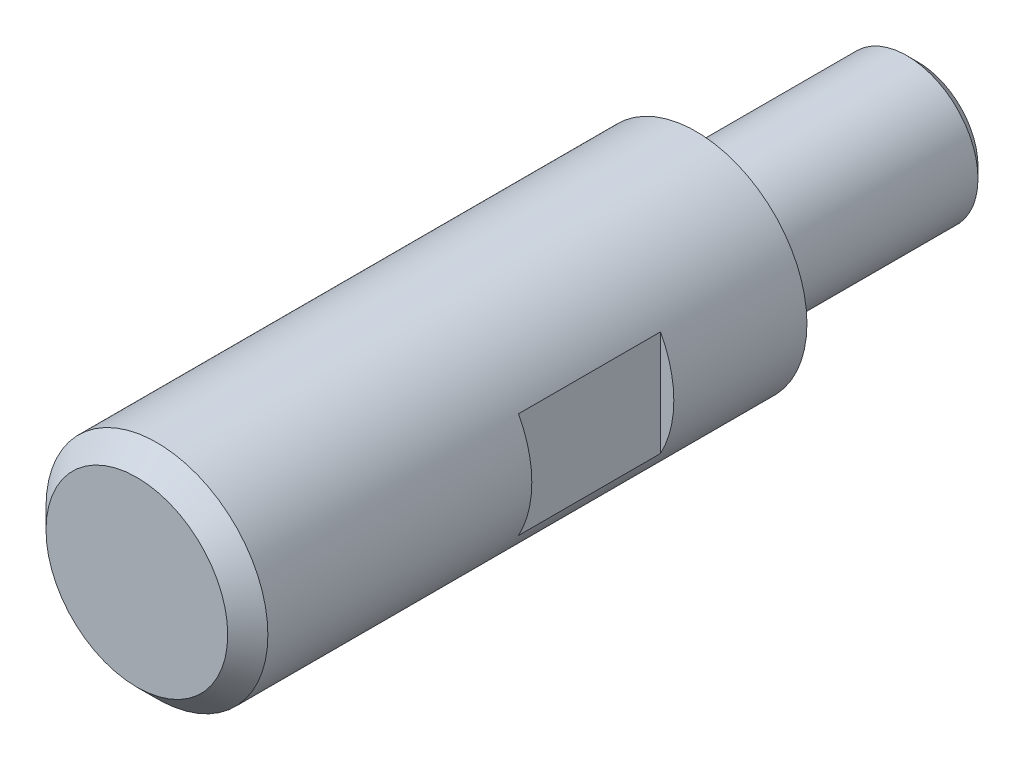
SolidWorks part; units mm, degrees
ref_plane "Płaszczyzna przednia" through (0, 0, 0) normal (0, 0, 1) x (1, 0, 0)
ref_plane "Płaszczyzna górna" through (0, 0, 0) normal (0, 1, 0) x (1, 0, 0)
ref_plane "Płaszczyzna prawa" through (0, 0, 0) normal (1, 0, 0) x (0, 0, -1)
sketch "Szkic1" plane through (0, 0, 0) normal (0, 1, 0) x (1, 0, 0)
  line L0 (11, -40) -> (11, -56)
  line L1 (11, -56) -> (15, -56)
  line L2 (15, -56) -> (15, -40)
  line L3 (15, -40) -> (11, -40)
sketch "Szkic2" plane through (0, 0, 0) normal (0, 1, 0) x (1, 0, 0)
  line L0 (-15, -40) -> (-15, -56)
  line L1 (-15, -56) -> (-11, -56)
  line L2 (-11, -56) -> (-11, -40)
  line L3 (-11, -40) -> (-15, -40)
sketch "Szkic3" plane through (0, 0, 0) normal (1, 0, 0) x (0, 0, -1)
  line L0 (-25, 0) -> (-25, 8)
  line L1 (-25, 8) -> (-1.227, 8)
  line L2 (-1.227, 8) -> (0, 6.773)
  line L3 (0, 6.773) -> (0, 0)
  line L4 (0, 0) -> (-25, 0)
  line L5 (0, 0) -> (-25, 0) construction
sketch "Szkic4" plane through (0, 0, 0) normal (1, 0, 0) x (0, 0, -1)
  line L0 (-88, 0) -> (-88, 12.5)
  line L1 (-88, 12.5) -> (-25, 12.5)
  line L2 (-25, 12.5) -> (-25, 0)
  line L3 (-25, 0) -> (-88, 0)
  line L4 (-25, 0) -> (-88, 0) construction
sketch "Szkic5" plane through (0, 0, 0) normal (1, 0, 0) x (0, 0, -1)
  line L0 (-88, 10.2373) -> (-85.7373, 12.5)
  line L1 (-85.7373, 12.5) -> (-88, 12.5)
  line L2 (-88, 12.5) -> (-88, 10.2373)
  line L3 (-25, 0) -> (-88, 0) construction
sketch "Szkic6" plane through (0, 0, 0) normal (1, 0, 0) x (0, 0, -1)
  line L0 (-23.4, 8) -> (-25, 8)
  line L1 (0, 0) -> (-25, 0) construction
  arc A0 (-25, 8) -> (-23.4, 8) centre (-24.2, 8) ccw
revolve "Obrót1" add sketch "Szkic3" angle 360 about L5 reverse direction yes
cosmetic thread "Oznaczenie gwintu1" parameters "D1"=23.4, "D2"=13.546
revolve "Obrót2" add sketch "Szkic4" angle 360 about L4 reverse direction yes
revolve "Wycięcie-obrót1" cut sketch "Szkic5" angle 360 about L3 reverse direction yes
revolve "Wycięcie-obrót2" cut sketch "Szkic6" angle 360 about L1 reverse direction yes
extrude "Wytnij-wyciągnięcie1" cut sketch "Szkic1" along normal blind 12.5 and the other way blind 12.5
extrude "Wytnij-wyciągnięcie2" cut sketch "Szkic2" along normal blind 12.5 and the other way blind 12.5
ref_plane "IP1 XY" through (0, 0, 0) normal (0, 0, 1) x (1, 0, 0)
ref_plane "IP1 XZ" through (0, 0, 0) normal (0, -1, 0) x (-1, 0, 0)
ref_plane "IP1 YZ" through (0, 0, 0) normal (1, 0, 0) x (0, 0, -1)
ref_axis "IP1 X" through (-80.9, 0, 0) along (1, 0, 0)
ref_axis "IP1 Y" through (0, -50, 0) along (0, 1, 0)
ref_axis "IP1 Z" through (0, 0, 80.9) along (0, 0, -1)
sketch3d "IP1"
  point P0 (0, 0, 0)
